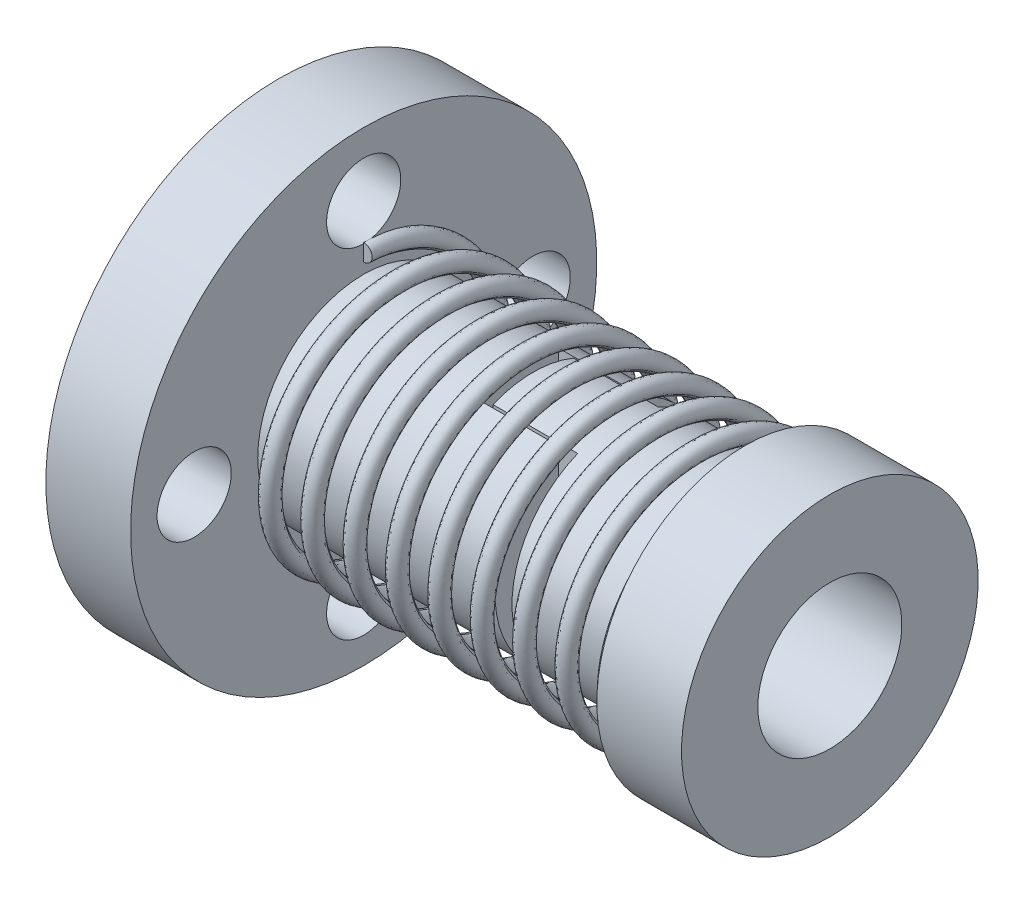
SolidWorks part; units mm, degrees
material "Chromium Copper, UNS C18200"
ref_plane "Front Plane" through (0, 0, 0) normal (0, 0, 1) x (1, 0, 0)
ref_plane "Top Plane" through (0, 0, 0) normal (0, 1, 0) x (1, 0, 0)
ref_plane "Right Plane" through (0, 0, 0) normal (1, 0, 0) x (0, 0, -1)
sketch "Sketch1" plane through (0, 0, 0) normal (0, 0, 1) x (1, 0, 0)
  line L0 (0, 0) -> (26, 0) construction
  line L1 (26, 0) -> (26, 7)
  line L2 (26, 7) -> (22, 7)
  line L3 (22, 7) -> (22, 5)
  line L4 (22, 5) -> (4, 5)
  line L5 (4, 5) -> (4, 11)
  line L6 (4, 11) -> (0, 11)
  line L7 (0, 11) -> (0, 0)
  line L8 (0, 0) -> (26, 0)
  point P8 (2, 11)
  dimension "D1" = 4
  dimension "D2" = 4
  dimension "D3" = 26
  dimension "D4" = 360
  dimension "D5" = 5
  dimension "D6" = 11
  dimension "D7" = 7
revolve "Revolve1" add sketch "Sketch1" angle 360 about L0
sketch "Sketch2" plane through (0, 0, 0) normal (0, 1, 0) x (1, 0, 0)
  line L0 (16, 6.9) -> (16, 1.9)
  line L1 (16, 1.9) -> (12, 1.9)
  line L2 (12, 1.9) -> (12, -1.9)
  line L3 (12, -1.9) -> (16, -1.9)
  line L4 (16, -1.9) -> (16, -6.9)
  line L5 (16, -6.9) -> (15.2, -6.9)
  line L7 (15.2, -6.9) -> (15.2, -2)
  line L8 (15.2, -2) -> (11.2, -2)
  line L9 (11.2, -2) -> (11.2, 2)
  line L10 (11.2, 2) -> (15.2, 2)
  line L11 (15.2, 2) -> (15.2, 6.9)
  line L12 (15.2, 6.9) -> (16, 6.9)
  line L13 (22, 0) -> (4, 0) construction
  line L14 (22, 7) -> (22, -7) construction
  dimension "D1" = 0.8
  dimension "D2" = 3.8
  dimension "D3" = 1.9
  dimension "D4" = 2
  dimension "D5" = 2
  dimension "D6" = 6
  dimension "D7" = 4
  dimension "D8" = 4
  dimension "D9" = 5
  dimension "D10" = 5
extrude "Cut-Extrude1" cut sketch "Sketch2" against normal through all both and the other way through all
sketch "Sketch6" plane through (0, 0, 0) normal (-1, 0, 0) x (0, 0, 1)
  point P0 (0, 0)
sketch "Sketch9" plane through (0, 0, 0) normal (-1, 0, 0) x (0, 0, 1)
  point P0 (0, 0)
sketch "Sketch13" plane through (0, 0, 0) normal (-1, 0, 0) x (0, 0, 1)
  point P0 (0, 0)
hole_wizard "M8 Tapped Hole3" positions "Sketch13" profile "Sketch12" tap size "M8" standard "ISO" end condition through all
sketch "Sketch12" plane through (0, 0, 0) normal (0, 1, 0) x (0, 0, 1)
  line L0 (0, 0) -> (0, 26)
  line L1 (0, 26) -> (3.4, 26)
  line L2 (3.4, 26) -> (3.4, 0.625)
  line L3 (3.4, 0.625) -> (4.025, 0)
  line L5 (4.025, 0) -> (0, 0)
  line L6 (-3.4, 0.625) -> (-4.025, 0) construction
  line L11 (0, -6.35) -> (0, 107.95) construction
  dimension "Thru Tap Drill Dia." = 6.8
  dimension "Thru Tap Drill Depth" = 26
  dimension "Near C'Sink Dia." = 8.05
  dimension "Near C'Sink Angle" = 90
cosmetic thread "Hole Thread3" parameters "D2"=8
sketch "Sketch14" plane through (4, 0, 0) normal (1, 0, 0) x (0, 0, -1)
  circle A0 centre (0, 0) radius 5.9
  dimension "11" = 11.8
curve "Helix/Spiral3" pitch 2 height 18 turns 9
sketch "Sketch15" plane through (0, 0, 0) normal (0, 0, 1) x (1, 0, 0)
  line L0 (4, -11) -> (4, 11) construction
  circle A0 centre (4, 5.9) radius 0.4
  spline S0 degree 3 poles (4, 5.9) (4.0414, 5.9) (4.1251, 5.5928) (4.25, 4.2805) (4.375, 2.3166) (4.5, 0) (4.625, -2.3166) (4.75, -4.2805) (4.875, -5.5928) (5, -6.0536) (5.125, -5.5928) (5.25, -4.2805) (5.4167, -1.662) (5.5833, 1.662) (5.75, 4.2805) (5.875, 5.5928) (6, 6.0536) (6.125, 5.5928) (6.25, 4.2805) (6.4167, 1.662) (6.5833, -1.662) (6.75, -4.2805) (6.875, -5.5928) (7, -6.0536) (7.125, -5.5928) (7.25, -4.2805) (7.4167, -1.662) (7.5833, 1.662) (7.75, 4.2805) (7.875, 5.5928) (8, 6.0536) (8.125, 5.5928) (8.25, 4.2805) (8.4167, 1.662) (8.5833, -1.662) (8.75, -4.2805) (8.875, -5.5928) (9, -6.0536) (9.125, -5.5928) (9.25, -4.2805) (9.4167, -1.662) (9.5833, 1.662) (9.75, 4.2805) (9.875, 5.5928) (10, 6.0536) (10.125, 5.5928) (10.25, 4.2805) (10.4167, 1.662) (10.5833, -1.662) (10.75, -4.2805) (10.875, -5.5928) (11, -6.0536) (11.125, -5.5928) (11.25, -4.2805) (11.4167, -1.662) (11.5833, 1.662) (11.75, 4.2805) (11.875, 5.5928) (12, 6.0536) (12.125, 5.5928) (12.25, 4.2805) (12.4167, 1.662) (12.5833, -1.662) (12.75, -4.2805) (12.875, -5.5928) (13, -6.0536) (13.125, -5.5928) (13.25, -4.2805) (13.4167, -1.662) (13.5833, 1.662) (13.75, 4.2805) (13.875, 5.5928) (14, 6.0536) (14.125, 5.5928) (14.25, 4.2805) (14.4167, 1.662) (14.5833, -1.662) (14.75, -4.2805) (14.875, -5.5928) (15, -6.0536) (15.125, -5.5928) (15.25, -4.2805) (15.4167, -1.662) (15.5833, 1.662) (15.75, 4.2805) (15.875, 5.5928) (16, 6.0536) (16.125, 5.5928) (16.25, 4.2805) (16.4167, 1.662) (16.5833, -1.662) (16.75, -4.2805) (16.875, -5.5928) (17, -6.0536) (17.125, -5.5928) (17.25, -4.2805) (17.4167, -1.662) (17.5833, 1.662) (17.75, 4.2805) (17.875, 5.5928) (18, 6.0536) (18.125, 5.5928) (18.25, 4.2805) (18.4167, 1.662) (18.5833, -1.662) (18.75, -4.2805) (18.875, -5.5928) (19, -6.0536) (19.125, -5.5928) (19.25, -4.2805) (19.4167, -1.662) (19.5833, 1.662) (19.75, 4.2805) (19.875, 5.5928) (20, 6.0536) (20.125, 5.5928) (20.25, 4.2805) (20.4167, 1.662) (20.5833, -1.662) (20.75, -4.2805) (20.875, -5.5928) (21, -6.0536) (21.125, -5.5928) (21.25, -4.2805) (21.375, -2.3166) (21.5, 0) (21.625, 2.3166) (21.75, 4.2805) (21.8749, 5.5928) (21.9586, 5.9) (22, 5.9) knots 0 0 0 0 0.006944 0.013889 0.020833 0.027778 0.034722 0.041667 0.048611 0.055556 0.0625 0.069444 0.076389 0.090278 0.097222 0.104167 0.111111 0.118056 0.125 0.131944 0.145833 0.152778 0.159722 0.166667 0.173611 0.180556 0.1875 0.201389 0.208333 0.215278 0.222222 0.229167 0.236111 0.243056 0.256944 0.263889 0.270833 0.277778 0.284722 0.291667 0.298611 0.3125 0.319444 0.326389 0.333333 0.340278 0.347222 0.354167 0.368056 0.375 0.381944 0.388889 0.395833 0.402778 0.409722 0.423611 0.430556 0.4375 0.444444 0.451389 0.458333 0.465278 0.479167 0.486111 0.493056 0.5 0.506944 0.513889 0.520833 0.534722 0.541667 0.548611 0.555556 0.5625 0.569444 0.576389 0.590278 0.597222 0.604167 0.611111 0.618056 0.625 0.631944 0.645833 0.652778 0.659722 0.666667 0.673611 0.680556 0.6875 0.701389 0.708333 0.715278 0.722222 0.729167 0.736111 0.743056 0.756944 0.763889 0.770833 0.777778 0.784722 0.791667 0.798611 0.8125 0.819444 0.826389 0.833333 0.840278 0.847222 0.854167 0.868056 0.875 0.881944 0.888889 0.895833 0.902778 0.909722 0.923611 0.930556 0.9375 0.944444 0.951389 0.958333 0.965278 0.972222 0.979167 0.986111 0.993056 1 1 1 1 construction
  dimension "0.8" = 0.8
sweep "Sweep1" add profiles "Sketch15" path "Helix/Spiral3"
sketch "Sketch16" plane through (0, 0, 0) normal (-1, 0, 0) x (0, 0, 1)
  circle A0 centre (0, 8) radius 1.75
  circle A3 centre (8, 0) radius 1.75
  circle A4 centre (0, -8) radius 1.75
  circle A5 centre (-8, 0) radius 1.75
  point P16 (0, 0)
  dimension "D1" = 3.5
  dimension "D2" = 4
  dimension "8" = 8
extrude "Cut-Extrude2" cut sketch "Sketch16" against normal up to surface (4 mm away) and the other way through all up to face at (4, -5, 0)
